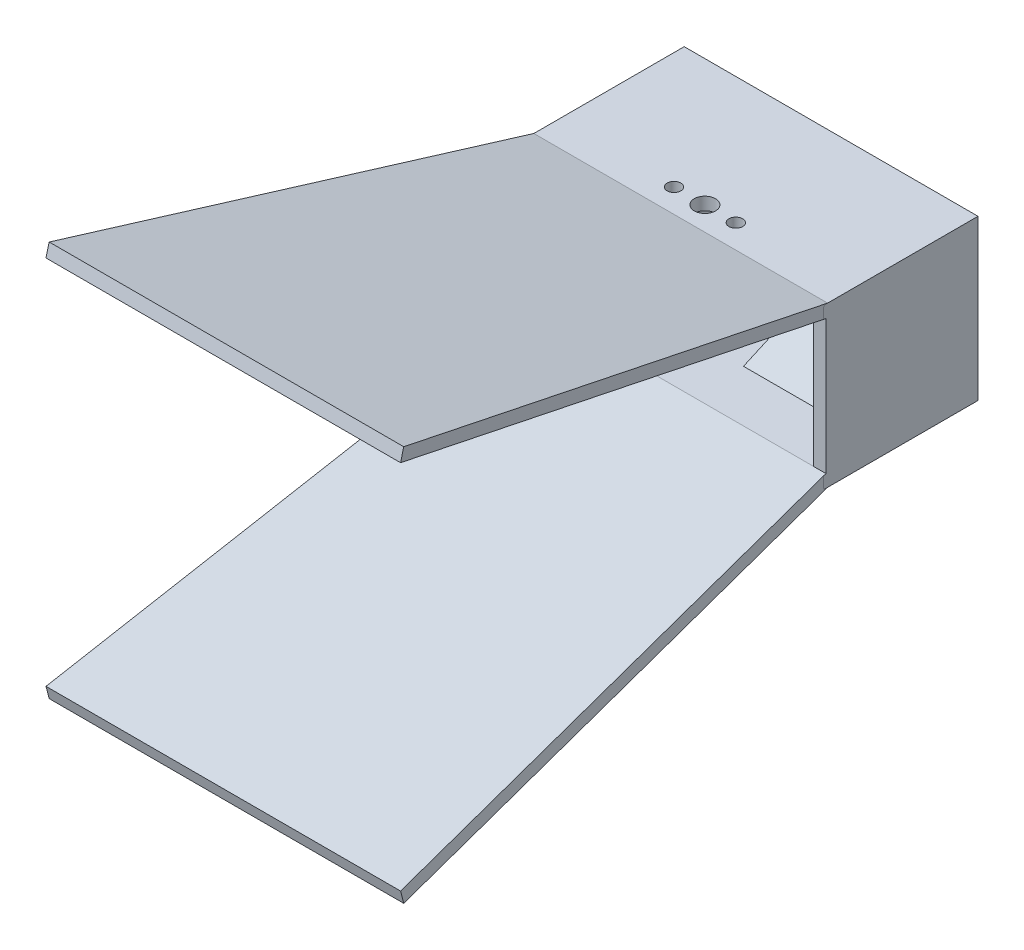
SolidWorks part; units mm, degrees
ref_plane "Alzado" through (0, 0, 0) normal (0, 0, 1) x (1, 0, 0)
ref_plane "Planta" through (0, 0, 0) normal (0, 1, 0) x (1, 0, 0)
ref_plane "Vista lateral" through (0, 0, 0) normal (1, 0, 0) x (0, 0, -1)
sketch "Croquis1" plane through (0, 0, 0) normal (0, 0, 1) x (1, 0, 0)
  line L1 (-26.5, -13.25) -> (26.5, -13.25)
  line L2 (-26.5, -13.25) -> (-26.5, 13.25)
  line L3 (-26.5, 13.25) -> (26.5, 13.25)
  line L4 (26.5, -13.25) -> (26.5, 13.25)
  line L5 (-26.5, -13.25) -> (26.5, 13.25) construction
  line L6 (-26.5, 13.25) -> (26.5, -13.25) construction
  point P0 (0, 0)
  dimension "D1" = 26.5
  dimension "D2" = 53
extrude "Saliente-Extruir1" add sketch "Croquis1" along normal blind 14.8
sketch "Croquis5" plane through (0, 0, 14.8) normal (0, 0, 1) x (1, 0, 0)
  line L0 (-26.5, 13.25) -> (-26.5, -13.25)
  line L1 (-26.5, -13.25) -> (26.5, -13.25)
  line L2 (26.5, -13.25) -> (26.5, 13.25)
  line L3 (26.5, 13.25) -> (-26.5, 13.25)
  point P4 (0, 0)
  dimension "D1" = 26.5
  dimension "D2" = 53
sketch "Croquis6" plane through (0, 0, 0) normal (0, 0, -1) x (-1, 0, 0)
  line L0 (0, 13.25) -> (0, 6.625) construction
  line L1 (-13.25, -6.625) -> (13.25, -6.625)
  line L2 (-13.25, -6.625) -> (-13.25, 6.625)
  line L3 (-13.25, 6.625) -> (13.25, 6.625)
  line L4 (13.25, -6.625) -> (13.25, 6.625)
  line L5 (-26.5, 13.25) -> (26.5, 13.25) construction
  line L6 (0, -6.625) -> (0, -13.25) construction
  line L7 (26.5, -13.25) -> (-26.5, -13.25) construction
  point P0 (0, 0)
  dimension "D1" = 13.25
  dimension "D2" = 26.5
loft "Cortar-Recubrir3" cut profiles "Croquis5", "Croquis6" connector at (-26.5, -13.25, 14.8) connector at (-13.25, -6.625, 0)
sketch "Croquis8" plane through (0, 0, 0) normal (0, 0, -1) x (-1, 0, 0)
  line L1 (2.5, -13.25) -> (-2.5, -13.25)
  line L2 (2.5, -13.25) -> (2.5, 13.25)
  line L3 (2.5, 13.25) -> (-2.5, 13.25)
  line L4 (-2.5, -13.25) -> (-2.5, 13.25)
  line L5 (2.5, -13.25) -> (-2.5, 13.25) construction
  line L6 (2.5, 13.25) -> (-2.5, -13.25) construction
  point P0 (0, 0)
  dimension "D1" = 5
  dimension "D2" = 26.5
extrude "Cortar-Extruir2" cut sketch "Croquis8" against normal blind 14.8
sketch "Croquis10" plane through (0, 0, 0) normal (1, 0, 0) x (0, 0, -1)
  line L0 (-14.8, 13.25) -> (-25, 13.25)
  line L1 (-25, 13.25) -> (-115, 36.6154)
  line L2 (-115, 36.6154) -> (-115, 13.25) construction
  line L3 (-115, 13.25) -> (-25, 13.25) construction
  line L4 (-115, 36.6154) -> (-114.3718, 39.0352)
  line L5 (-14.8, -13.25) -> (0, -13.25)
  line L6 (5, 15) -> (5, 15.75)
  line L7 (5, 15.75) -> (-24.6808, 15.75)
  line L8 (-24.6808, 15.75) -> (-114.3718, 39.0352)
  line L9 (5, 15) -> (5, -15.75)
  line L10 (-14.8, -13.25) -> (-25, -13.25)
  line L11 (-25, -13.25) -> (-115, -36.6154)
  line L12 (0, -13.25) -> (0, 13.25) construction
  line L13 (-25, 13.25) -> (-25, -13.25) construction
  line L14 (-24.6808, 15.75) -> (-24.6808, -15.75) construction
  line L15 (5, -15.75) -> (-24.6808, -15.75)
  line L16 (-115, -36.6154) -> (-114.3718, -39.0352)
  line L17 (-114.3718, -39.0352) -> (-24.6808, -15.75)
  line L19 (-115, -13.25) -> (-25, -13.25) construction
  line L20 (-115, -13.25) -> (-115, -36.6154) construction
  line L21 (0, -13.25) -> (0, 13.25)
  line L22 (0, 13.25) -> (-14.8, 13.25)
  dimension "D1" = 23.3654
  dimension "D2" = 2.5
  dimension "D3" = 10.2
  dimension "D4" = 2.5
  dimension "D5" = 5
  dimension "D6" = 2.5
  dimension "D7" = 23.3654
  dimension "D8" = 2.5
  dimension "D9" = 90
extrude "Saliente-Extruir2" add sketch "Croquis10" along normal blind 35 and the other way blind 35
sketch "Croquis12" plane through (0, 0, 0) normal (0, 0, 1) x (1, 0, 0)
  line L0 (26.5, 13.25) -> (35, 13.25) construction
  line L1 (-26.5, -13.25) -> (26.5, -13.25)
  line L2 (-26.5, -13.25) -> (-26.5, 13.25)
  line L3 (-26.5, 13.25) -> (26.5, 13.25)
  line L4 (26.5, -13.25) -> (26.5, 13.25)
  line L5 (-26.5, -13.25) -> (26.5, 13.25) construction
  line L6 (-26.5, 13.25) -> (26.5, -13.25) construction
  line L7 (-29, -13.25) -> (29, -13.25)
  line L8 (-29, -13.25) -> (-29, 13.25)
  line L9 (-29, 13.25) -> (29, 13.25)
  line L10 (29, -13.25) -> (29, 13.25)
  line L11 (-29, -13.25) -> (29, 13.25) construction
  line L12 (-29, 13.25) -> (29, -13.25) construction
  point P0 (0, 0)
  point P5 (0, 0)
  dimension "D1" = 2.5
  dimension "D2" = 53
  dimension "D3" = 26.5
extrude "Saliente-Extruir3" add sketch "Croquis12" along normal blind 25 contours L9 L8 L7 L2 | L7 L10 L9 L4 region at (-27.75, 0, 0) region at (27.75, 0, 0)
sketch "Croquis13" plane through (0, 15.75, 0) normal (0, 1, 0) x (1, 0, 0)
  line L0 (-35, -24.6808) -> (35, 5)
  line L1 (35, -24.6808) -> (-35, -24.6808)
  line L2 (35, -24.6808) -> (35, 5)
  line L3 (35, 5) -> (-35, 5)
  line L4 (-35, -24.6808) -> (-35, 5)
  line L5 (35, -24.6808) -> (-35, 5)
  line L7 (-29, -24.6808) -> (29, -24.6808)
  line L8 (-29, -24.6808) -> (-29, 5)
  line L9 (-29, 5) -> (29, 5)
  line L10 (29, -24.6808) -> (29, 5)
  line L11 (-29, -24.6808) -> (29, 5) construction
  line L12 (-29, 5) -> (29, -24.6808) construction
  point P4 (0, -9.8404)
  line M1 (-35, -24.6808) -> (35, -24.6808)
  line M2 (35, -24.6808) -> (35, 5)
  line M3 (35, 5) -> (-35, 5)
  line M4 (-35, 5) -> (-35, -24.6808)
  dimension "D1" = 6
  dimension "D2" = 29.6808
  dimension "D3" = 70
  dimension "D4" = 58
extrude "Cortar-Extruir3" cut sketch "Croquis13" against normal blind 31.5 contours L0 L8 L5 M4 | L5 L8 L3 | L8 L0 M1 | L10 L5 M1 | L10 L5 L0 M2 | L10 L0 M3 region at (-32.0938, 15.75, 9.8404) region at (-31, 15.75, 23.8327) region at (-31, 15.75, -4.152) region at (31, 15.75, 23.8327) region at (31, 15.75, -4.152) region at (32.0938, 15.75, 9.8404)
sketch "Croquis14" plane through (0, 8.7526, -2.2723) normal (0, 0.9679, -0.2513) x (1, 0, 0)
  line L0 (29, -27.8466) -> (35, -27.8466)
  line L1 (35, -27.8466) -> (35, -120.5109)
  line L3 (-35, -120.5109) -> (-35, -27.8466)
  line L4 (-35, -27.8466) -> (-29, -27.8466)
  line L5 (29, -27.8466) -> (35, -120.5109)
  line L6 (-29, -27.8466) -> (-35, -120.5109)
  line M2 (35, -120.5109) -> (35, -27.8466)
  line M3 (35, -27.8466) -> (29, -27.8466)
  line M5 (-29, -27.8466) -> (-35, -27.8466)
  line M6 (-35, -27.8466) -> (-35, -120.5109)
  dimension "D1" = 92.6643
  dimension "D3" = 6
  dimension "D4" = 70
  dimension "D2" = 6
extrude "Cortar-Extruir13" cut sketch "Croquis14" against normal blind 2.5 contours L6 M5 M6 | L6 | L3 L6 | L1 L5 M3 | L5 | L5 M2 region at (33, 23.5117, 54.5778) region at (-33, 23.5117, 54.5778)
sketch "Croquis16" plane through (0, -8.7526, -2.2723) normal (0, -0.9679, -0.2513) x (1, 0, 0)
  line L0 (-29, 27.8466) -> (-35, 27.8466)
  line L1 (-35, 27.8466) -> (-35, 120.5109)
  line L3 (35, 120.5109) -> (35, 27.8466)
  line L4 (35, 27.8466) -> (29, 27.8466)
  line L5 (29, 27.8466) -> (35, 120.5109)
  line L6 (-29, 27.8466) -> (-35, 120.5109)
  line M2 (-35, 120.5109) -> (-35, 27.8466)
  line M3 (-35, 27.8466) -> (-29, 27.8466)
  line M5 (29, 27.8466) -> (35, 27.8466)
  line M6 (35, 27.8466) -> (35, 120.5109)
  dimension "D1" = 92.6643
  dimension "D2" = 6
  dimension "D3" = 6
  dimension "D4" = 70
extrude "Cortar-Extruir14" cut sketch "Croquis16" against normal blind 2.5 contours L5 M5 M6 | L5 | L3 L5 | L6 M2 | L6 | L1 L6 M3 region at (-33, -23.5117, 54.5778) region at (33, -23.5117, 54.5778)
sketch "Croquis17" plane through (0, 0, -5) normal (0, 0, -1) x (-1, 0, 0)
  line L1 (-29, -15.75) -> (29, -15.75)
  line L2 (-29, -15.75) -> (-29, 15.75)
  line L3 (-29, 15.75) -> (29, 15.75)
  line L4 (29, -15.75) -> (29, 15.75)
  line L5 (-29, -15.75) -> (29, 15.75) construction
  line L6 (-29, 15.75) -> (29, -15.75) construction
  line L7 (-35, -15.75) -> (35, -15.75)
  line L8 (-35, -15.75) -> (-35, 15.75)
  line L9 (-35, 15.75) -> (35, 15.75)
  line L10 (35, -15.75) -> (35, 15.75)
  line L11 (-35, -15.75) -> (35, 15.75) construction
  line L12 (-35, 15.75) -> (35, -15.75) construction
  point P0 (0, 0)
  point P1 (0, 0)
  point P5 (0, 0)
  point P9 (0, 0)
  line M2 (-29, 15.75) -> (-29, -15.75)
  line M4 (29, -15.75) -> (29, 15.75)
  dimension "D1" = 31.5
  dimension "D2" = 70
  dimension "D3" = 58
  dimension "D4" = 31.5
extrude "Cortar-Extruir11" cut sketch "Croquis17" against normal blind 30.5 contours M2 | M4 region at (32, 0, -5) region at (-32, 0, -5)
sketch "Croquis18" plane through (0, 15.75, 0) normal (0, 1, 0) x (1, 0, 0)
  line L0 (-29, 5) -> (29, 5) construction
  line L1 (-29, 5) -> (29, 5) construction
  circle A0 centre (0.0814, -19.9999) radius 2.1
  circle A1 centre (6.1814, -20) radius 1.35
  circle A2 centre (-6.0186, -20) radius 1.35
  point P2 (0, 5)
  dimension "D1" = 4.2
  dimension "D3" = 2.7
  dimension "D4" = 2.7
  dimension "D2" = 25
  dimension "D5" = 6.1
  dimension "D6" = 6.1
  dimension "D7" = 25
  dimension "D8" = 25
extrude "Cortar-Extruir12" cut sketch "Croquis18" against normal blind 2.5
equation "\"CAJA_H\"= 30"
equation "\"D1@Croquis1\"=\"A_CAJA\""
equation "\"CAJA_W\"= 46"
equation "\"D2@Croquis1\"=\"W_CAJA\""
equation "\"D1@Croquis6\"=\"A_CONC\""
equation "\"D2@Croquis6\"=\"W_CONC\""
equation "\"D1@Croquis7\" = \"CAJA_H\""
equation "\"J_D\"= 6"
equation "\"D1@Croquis8\" = \"E_ALETA\""
equation "\"D2@Croquis8\"=\"A_CAJA\""
equation "\"G\"= 2.5"
equation "\"D6@Croquis10\"=\"E_CAJA\""
equation "\"D4@Croquis10\"=\"E_CAJA\""
equation "\"H\"= 39"
equation "\"D1@Croquis10\" = \"H\""
equation "\"L\"= 70"
equation "\"D2@Croquis10\" = \"L\""
equation "\"L2\"= 27"
equation "\"D3@Croquis10\"=\"L_CAJA\"-\"L_CONC\""
equation "\"D7@Croquis10\" = \"H\""
equation "\"D2@Croquis10\"=\"E_CAJA\""
equation "\"D8@Croquis10\"=\"E_CAJA\""
equation "\"D1@Croquis12\"=\"E_CAJA\""
equation "\"D1@Croquis13\" = \"CAJA_H\""
equation "\"R\"= 4.15"
equation "\"D1@Croquis18\"=( 2 * \"R_SONDA\" ) +\"TOLERANCIA\""
equation "\"BASE\"= 14"
equation "\"D1@Croquis10\"=\"A_ALETA\"-\"A_BASE\""
equation "\"D7@Croquis10\"=\"A_ALETA\"-\"A_BASE\""
equation "\"D9@Croquis10\"=\"L_ALETA\""
equation "\"A_ALETA\"= ( ( ( tan ( \"ANG_ALETA\" ) ) * \"L_ALETA\" ) + \"A_BASE\" - ( \"GAP_ALETAS\" / 2 ) )"
equation "\"A_BASE\"= ( \"L_DIE\" - \"E_CAJA\" )"
equation "\"L_ALETA\"=90.000000"
equation "\"TAU_ALETA\"= ( \"L_ALETA\" / ( log ( ( \"A_ALETA\" ) + 1 ) ) )"
equation "\"E_ALETA\"=5.000000"
equation "\"R_SONDA\"= 2.05"
equation "\"D_SONDA\"=20.000000"
equation "\"L_CAJA\"=25.000000"
equation "\"E_CAJA\"= 2.5"
equation "\"A_CAJA\"= ( 2 * \"A_BASE\" ) + \"GAP_ALETAS\""
equation "\"W_CAJA\"= \"A_CAJA\" * \"CONST_CAJA\""
equation "\"W_CONC\"= ( \"W_CAJA\" / \"CONST_CONC\" ) "
equation "\"A_CONC\"= ( \"A_CAJA\" / \"CONST_CONC\" )"
equation "\"L_CONC\"= \"D_SONDA\" - \"OFFSET_CONC\""
equation "\"W_ALETA\"=70.000000"
equation "\"GAP_ALETAS\"=1.500000"
equation "\"D1@Saliente-Extruir1\"=\"L_CONC\""
equation "\"D1@Cortar-Extruir2\"=\"L_CONC\""
equation "\"D1@Saliente-Extruir2\"=\"W_ALETA\"/2"
equation "\"D2@Saliente-Extruir2\"=\"W_ALETA\"/2"
equation "\"D5@Croquis10\"=\"E_CAJA\"*2"
equation "\"D1@Saliente-Extruir3\"=\"L_CAJA\""
equation "\"D1@Croquis13\"=(\"W_ALETA\"-(\"W_CAJA\"+(2*\"E_CAJA\")))/2"
equation "\"D1@Cortar-Extruir8\" = \"E_CAJA\""
equation "\"D1@Cortar-Extruir3\" = ( \"A_CAJA\" + ( 2 * \"E_CAJA\" ) )"
equation "\"D1@Cortar-Extruir13\"=\"E_CAJA\""
equation "\"D1@Cortar-Extruir14\"=\"E_CAJA\""
equation "\"D1@Croquis17\" = \"A_CAJA\" + ( 2 * \"E_CAJA\" )"
equation "\"D2@Croquis17\" = \"W_ALETA\""
equation "\"D3@Croquis17\"=\"W_CAJA\" + (2 * \"E_CAJA\")"
equation "\"D4@Croquis17\"=\"A_CAJA\" + (2 * \"E_CAJA\")"
equation "\"D1@Cortar-Extruir11\"=\"L_CAJA\" + (2 * \"E_CAJA\") +0.5"
equation "\"D2@Croquis18\"=\"D_SONDA\"+ \"E_CAJA\"*2"
equation "\"D1@Cortar-Extruir12\"=\"E_CAJA\""
equation "\"L_DIE_SONDA\"= ( \"GAP_ALETAS\" / 4 )"
equation "\"CONST_CONC\"=2.000000"
equation "\"K\"= 1.5"
equation "\"L_DIE\"= 15"
equation "\"L_CI\"= 18"
equation "\"CONST_CAJA\"=2.000000"
equation "\"ANG_ALETA\"=15.000000"
equation "\"R_C_SONDA\"= 0.63"
equation "\"TOLERANCIA\"= 0.1"
equation "\"OFFSET_CONC\"= ( 2 * \"R_TORNILLO\" )"
equation "\"R_TORNILLO\"=2.600000"
equation "\"D4@Croquis18\"=\"R_TORNILLO\"+\"TOLERANCIA\""
equation "\"D3@Croquis18\"=\"R_TORNILLO\"+\"TOLERANCIA\""
equation "\"D7@Croquis18\"=\"D_SONDA\"+ \"E_CAJA\"*2"
equation "\"D8@Croquis18\"=\"D_SONDA\"+ \"E_CAJA\"*2"
